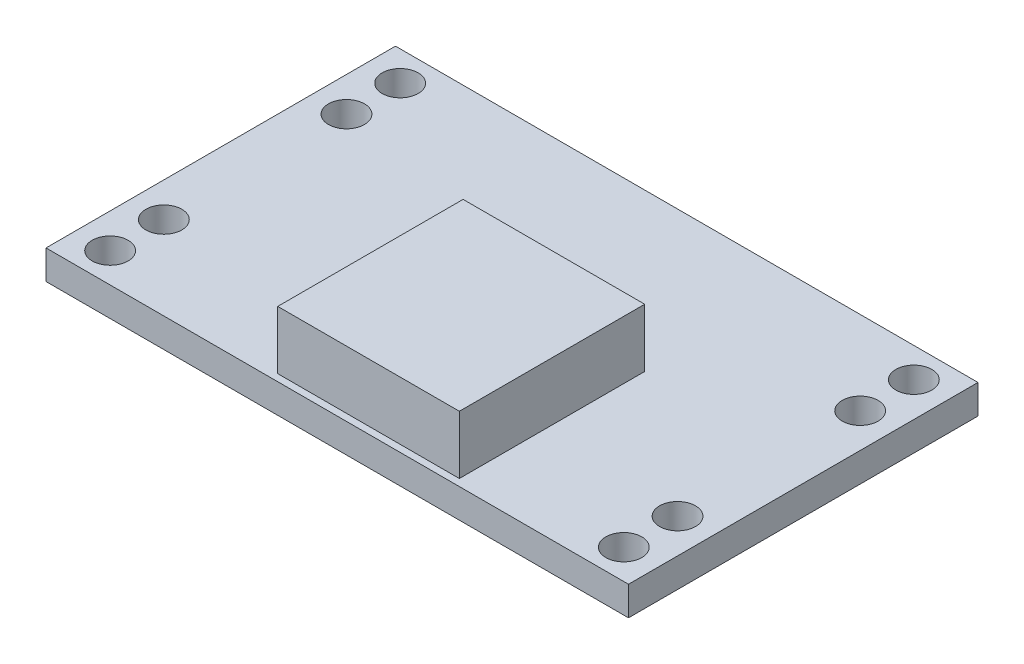
SolidWorks part; units mm, degrees
ref_plane "Front Plane" through (0, 0, 0) normal (0, 0, 1) x (1, 0, 0)
ref_plane "Top Plane" through (0, 0, 0) normal (0, 1, 0) x (1, 0, 0)
ref_plane "Right Plane" through (0, 0, 0) normal (1, 0, 0) x (0, 0, -1)
sketch "Sketch1" plane through (0, 0, 0) normal (0, 1, 0) x (1, 0, 0)
  line L1 (15, -9) -> (-15, -9)
  line L2 (15, -9) -> (15, 9)
  line L3 (15, 9) -> (-15, 9)
  line L4 (-15, -9) -> (-15, 9)
  line L5 (15, -9) -> (-15, 9) construction
  line L6 (15, 9) -> (-15, -9) construction
  point P0 (0, 0)
  dimension "D1" = 30
  dimension "D2" = 18
extrude "Boss-Extrude1" add sketch "Sketch1" along normal blind 1.5
sketch "Sketch2" plane through (0, 1.5, 0) normal (0, 1, 0) x (1, 0, 0)
  line L1 (-3.4244, 0.9062) -> (5.9286, 0.9062)
  line L2 (-3.4244, 0.9062) -> (-3.4244, -8.6405)
  line L3 (-3.4244, -8.6405) -> (5.9286, -8.6405)
  line L4 (5.9286, 0.9062) -> (5.9286, -8.6405)
  line L5 (-3.4244, 0.9062) -> (5.9286, -8.6405) construction
  line L6 (-3.4244, -8.6405) -> (5.9286, 0.9062) construction
  point P0 (1.2521, -3.8671)
extrude "Boss-Extrude2" add sketch "Sketch2" along normal blind 3
sketch "Sketch3" plane through (0, 1.5, 0) normal (0, 1, 0) x (1, 0, 0)
  circle A0 centre (-13.228, 7.4682) radius 0.9261
  circle A1 centre (-13.228, 4.7022) radius 0.9261
extrude "Cut-Extrude1" cut sketch "Sketch3" against normal through all
ref_axis "Axis1" through (0, 0, 0) along (0, 1, 0)
pattern_circular "CirPattern1" count 2 over 360 about axis through (0, 0, 0) along (0, 1, 0) of "Cut-Extrude1"
mirror "Mirror1" about plane through (0, 0, 0) normal (1, 0, 0) of "Cut-Extrude1", "CirPattern1"
